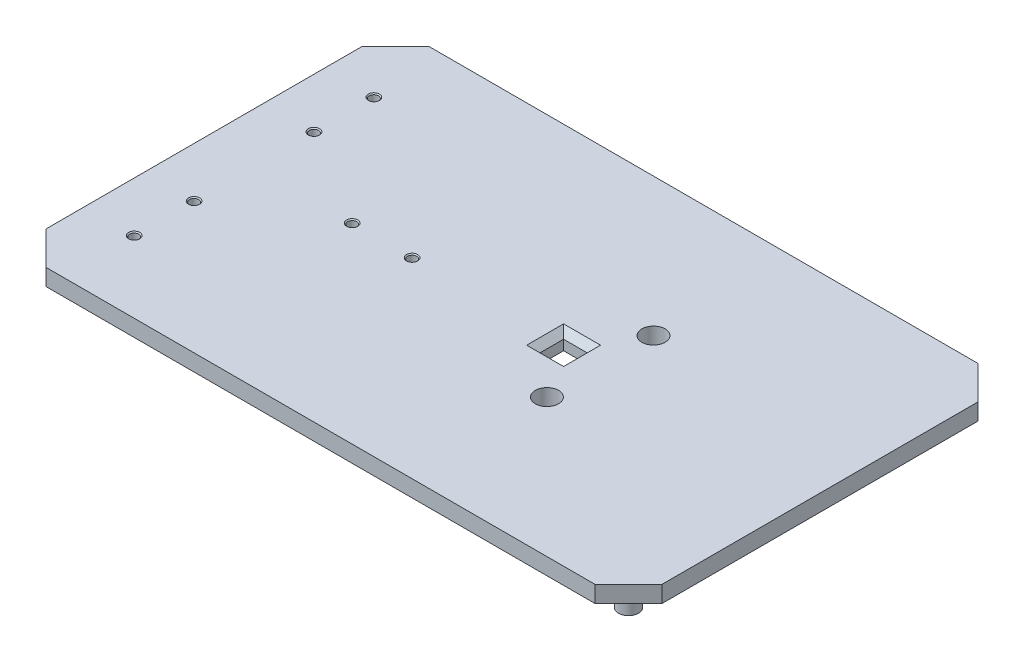
SolidWorks part; units mm, degrees
ref_plane "Front Plane" through (0, 0, 0) normal (0, 0, 1) x (1, 0, 0)
ref_plane "Top Plane" through (0, 0, 0) normal (0, 1, 0) x (1, 0, 0)
ref_plane "Right Plane" through (0, 0, 0) normal (1, 0, 0) x (0, 0, -1)
sketch "Sketch1" plane through (0, 0, 0) normal (0, 1, 0) x (1, 0, 0)
  line L1 (-92.5, 57.5) -> (92.5, 57.5)
  line L2 (-92.5, 57.5) -> (-92.5, -57.5)
  line L3 (-92.5, -57.5) -> (92.5, -57.5)
  line L4 (92.5, 57.5) -> (92.5, -57.5)
  circle A0 centre (26.5, 16) radius 1.375
  circle A1 centre (26.5, -16) radius 1.375
  circle A2 centre (-77.5, 36) radius 1.375
  circle A3 centre (-77.5, 18) radius 1.375
  circle A4 centre (-77.5, -18) radius 1.375
  circle A5 centre (-77.5, -36) radius 1.375
  circle A6 centre (-48, 0) radius 1.375
  circle A7 centre (-30, 0) radius 1.375
  dimension "D4" = 66
  dimension "D5" = 41.5
  dimension "D6" = 41.5
  dimension "D7" = 2.75
  dimension "D8" = 2.75
  dimension "D13" = 0
  dimension "D14" = 2.75
  dimension "D15" = 2.75
  dimension "D16" = 0
  dimension "D17" = 0
  dimension "D18" = 18
  dimension "D19" = 18
  dimension "D20" = 18
  dimension "D21" = 18
  dimension "D22" = 2.75
  dimension "D23" = 2.75
  dimension "D24" = 2.75
  dimension "D25" = 2.75
  dimension "D10" = 29.5
  dimension "D1" = 115
  dimension "D2" = 66
  dimension "D3" = 185
  dimension "D9" = 92.5
  dimension "D11" = 57.5
  dimension "D12" = 15
  dimension "D26" = 30
  dimension "D27" = 48
extrude "Boss-Extrude2" add sketch "Sketch1" along normal blind 5 contours L1 L4 L3 L2
sketch "Sketch6" plane through (0, 0, 0) normal (0, -1, 0) x (1, 0, 0)
ref_plane "Plane1" through (92.5, 5, 57.5) normal (1, 0, 0) x (0, 0, -1)
extrude "Cut-Extrude5" cut sketch "Sketch1<7>" along normal blind 15 and the other way blind 15 flip side to cut
sketch "Sketch1<7>" plane through (0, 0, 0) normal (0, 1, 0) x (1, 0, 0) same geometry as "Sketch1"
sketch "Sketch10" plane through (0, 0, 0) normal (0, 1, 0) x (1, 0, 0)
  line L0 (92.5, 57.5) -> (92.5, -57.5) construction
  line L1 (-92.5, 57.5) -> (92.5, 57.5) construction
  line L2 (92.5, -108.375) -> (92.5, -6.625) construction
  line L3 (-92.5, -57.5) -> (92.5, -57.5) construction
  circle A0 centre (26.5, 16) radius 3
  circle A1 centre (26.5, -16) radius 3
  circle A2 centre (82.5, -47.5) radius 3
  circle A3 centre (82.5, 47.5) radius 3
  dimension "D1" = 6
  dimension "D2" = 6
  dimension "D3" = 6
  dimension "D4" = 6
  dimension "D5" = 10
  dimension "D6" = 10
  dimension "D7" = 10
  dimension "D8" = 10
chamfer "Chamfer2" distance 0.3 angle 45 8 edges at (-77.5, 5, 37.375) (-77.5, 5, 19.375) (-77.5, 5, -34.625) (-77.5, 5, -16.625) (-48, 5, 1.375) (-30, 5, 1.375) (26.5, 5, -14.625) (26.5, 5, 17.375)
extrude "Boss-Extrude3" add sketch "Sketch10" against normal blind 6 contours A3 | A2
sketch "Sketch11" plane through (0, 0, 0) normal (0, 1, 0) x (1, 0, 0)
  circle A0 centre (26.5, -16) radius 4
  circle A3 centre (26.5, 16) radius 4
  dimension "D1" = 8
  dimension "D2" = 8
extrude "Boss-Extrude4" add sketch "Sketch11" against normal blind 4
sketch "Sketch13" plane through (0, 0, 0) normal (0, 1, 0) x (1, 0, 0)
  circle A0 centre (26.5, 16) radius 3.5
  circle A1 centre (26.5, -16) radius 3.5
  dimension "D1" = 7
  dimension "D2" = 7
extrude "Cut-Extrude6" cut sketch "Sketch13" against normal blind 3 and the other way blind 10 contours A1 | A0
sketch "Sketch14" plane through (0, 0, 0) normal (0, 1, 0) x (1, 0, 0)
  circle A0 centre (26.5, 16) radius 1.375
  circle A1 centre (26.5, -16) radius 1.375
  dimension "D1" = 2.75
  dimension "D2" = 2.75
extrude "Cut-Extrude8" cut sketch "Sketch14" against normal blind 7 and the other way blind 7
chamfer "Chamfer3" distance 1.625 angle 45 2 edges at (26.5, -3, 17.375) (26.5, -3, -14.625)
chamfer "Chamfer6" distance 10 angle 45 4 edges at (92.5, 2.5, 57.5) (92.5, 2.5, -57.5) (-92.5, 2.5, 57.5) (-92.5, 2.5, -57.5)
sketch "Sketch15" plane through (0, 5, 0) normal (0, 1, 0) x (1, 0, 0)
  line L0 (-82.5, -57.5) -> (82.5, -57.5) construction
  line L1 (19.05, 3.55) -> (11.95, 3.55)
  line L2 (19.05, 3.55) -> (19.05, -3.55)
  line L3 (19.05, -3.55) -> (11.95, -3.55)
  line L4 (11.95, 3.55) -> (11.95, -3.55)
  line L5 (-82.5, 57.5) -> (82.5, 57.5) construction
  line L6 (92.5, 47.5) -> (92.5, -47.5) construction
  dimension "D1" = 53.95
  dimension "D2" = 53.95
  dimension "D3" = 7.1
  dimension "D4" = 73.45
  dimension "D5" = 7.1
extrude "Cut-Extrude9" cut sketch "Sketch15" against normal blind 10 and the other way blind 10
chamfer "Chamfer7" distance 2 angle 45 4 edges at (15.5, 5, 3.55) (11.95, 5, 0) (15.5, 5, -3.55) (19.05, 5, 0)
